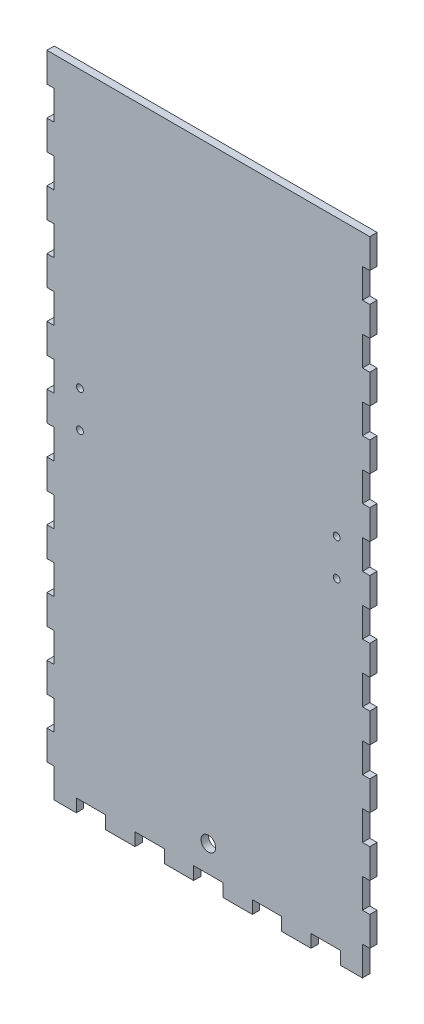
SolidWorks part; units mm, degrees
ref_plane "Front Plane" through (0, 0, 0) normal (0, 0, 1) x (1, 0, 0)
ref_plane "Top Plane" through (0, 0, 0) normal (0, 1, 0) x (1, 0, 0)
ref_plane "Right Plane" through (0, 0, 0) normal (1, 0, 0) x (0, 0, -1)
sketch "Sketch1" plane through (0, 0, 0) normal (0, 0, 1) x (1, 0, 0)
  line L0 (-66.675, 261.112) -> (-66.675, 248.412)
  line L1 (-66.675, 273.812) -> (66.675, 273.812)
  line L2 (-66.675, 273.812) -> (-66.675, 0)
  line L3 (-66.675, 0) -> (66.675, 0)
  line L4 (66.675, 273.812) -> (66.675, 0)
  line L5 (-66.675, 273.812) -> (-69.85, 273.812)
  line L6 (-66.675, 273.812) -> (-66.675, 261.112)
  line L7 (-66.675, 261.112) -> (-69.85, 261.112)
  line L8 (-69.85, 273.812) -> (-69.85, 261.112)
  line L13 (66.675, 273.812) -> (69.85, 273.812)
  line L14 (66.675, 273.812) -> (66.675, 261.112)
  line L15 (66.675, 261.112) -> (69.85, 261.112)
  line L16 (69.85, 273.812) -> (69.85, 261.112)
  line L17 (-66.675, 261.112) -> (-69.85, 261.112)
  line L18 (-69.85, 261.112) -> (-69.85, 248.412)
  line L19 (-66.675, 248.412) -> (-69.85, 248.412)
  line L20 (66.675, 261.112) -> (66.675, 248.412)
  line L21 (66.675, 261.112) -> (69.85, 261.112)
  line L22 (69.85, 261.112) -> (69.85, 248.412)
  line L23 (66.675, 248.412) -> (69.85, 248.412)
  line L24 (-66.675, 248.412) -> (-66.675, 235.712)
  line L25 (-66.675, 248.412) -> (-69.85, 248.412)
  line L26 (-69.85, 248.412) -> (-69.85, 235.712)
  line L27 (-66.675, 235.712) -> (-69.85, 235.712)
  line L28 (66.675, 248.412) -> (66.675, 235.712)
  line L29 (66.675, 248.412) -> (69.85, 248.412)
  line L30 (69.85, 248.412) -> (69.85, 235.712)
  line L31 (66.675, 235.712) -> (69.85, 235.712)
  line L32 (-66.675, 235.712) -> (-66.675, 223.012)
  line L33 (-66.675, 235.712) -> (-69.85, 235.712)
  line L34 (-69.85, 235.712) -> (-69.85, 223.012)
  line L35 (-66.675, 223.012) -> (-69.85, 223.012)
  line L36 (66.675, 235.712) -> (66.675, 223.012)
  line L37 (66.675, 235.712) -> (69.85, 235.712)
  line L38 (69.85, 235.712) -> (69.85, 223.012)
  line L39 (66.675, 223.012) -> (69.85, 223.012)
  line L40 (-66.675, 223.012) -> (-66.675, 210.312)
  line L41 (-66.675, 223.012) -> (-69.85, 223.012)
  line L42 (-69.85, 223.012) -> (-69.85, 210.312)
  line L43 (-66.675, 210.312) -> (-69.85, 210.312)
  line L44 (66.675, 223.012) -> (66.675, 210.312)
  line L45 (66.675, 223.012) -> (69.85, 223.012)
  line L46 (69.85, 223.012) -> (69.85, 210.312)
  line L47 (66.675, 210.312) -> (69.85, 210.312)
  line L48 (-66.675, 210.312) -> (-66.675, 197.612)
  line L49 (-66.675, 210.312) -> (-69.85, 210.312)
  line L50 (-69.85, 210.312) -> (-69.85, 197.612)
  line L51 (-66.675, 197.612) -> (-69.85, 197.612)
  line L52 (66.675, 210.312) -> (66.675, 197.612)
  line L53 (66.675, 210.312) -> (69.85, 210.312)
  line L54 (69.85, 210.312) -> (69.85, 197.612)
  line L55 (66.675, 197.612) -> (69.85, 197.612)
  line L56 (-66.675, 197.612) -> (-66.675, 184.912)
  line L57 (-66.675, 197.612) -> (-69.85, 197.612)
  line L58 (-69.85, 197.612) -> (-69.85, 184.912)
  line L59 (-66.675, 184.912) -> (-69.85, 184.912)
  line L60 (66.675, 197.612) -> (66.675, 184.912)
  line L61 (66.675, 197.612) -> (69.85, 197.612)
  line L62 (69.85, 197.612) -> (69.85, 184.912)
  line L63 (66.675, 184.912) -> (69.85, 184.912)
  line L64 (-66.675, 184.912) -> (-66.675, 172.212)
  line L65 (-66.675, 184.912) -> (-69.85, 184.912)
  line L66 (-69.85, 184.912) -> (-69.85, 172.212)
  line L67 (-66.675, 172.212) -> (-69.85, 172.212)
  line L68 (66.675, 184.912) -> (66.675, 172.212)
  line L69 (66.675, 184.912) -> (69.85, 184.912)
  line L70 (69.85, 184.912) -> (69.85, 172.212)
  line L71 (66.675, 172.212) -> (69.85, 172.212)
  line L72 (-66.675, 172.212) -> (-66.675, 159.512)
  line L73 (-66.675, 172.212) -> (-69.85, 172.212)
  line L74 (-69.85, 172.212) -> (-69.85, 159.512)
  line L75 (-66.675, 159.512) -> (-69.85, 159.512)
  line L76 (66.675, 172.212) -> (66.675, 159.512)
  line L77 (66.675, 172.212) -> (69.85, 172.212)
  line L78 (69.85, 172.212) -> (69.85, 159.512)
  line L79 (66.675, 159.512) -> (69.85, 159.512)
  line L80 (-66.675, 159.512) -> (-66.675, 146.812)
  line L81 (-66.675, 159.512) -> (-69.85, 159.512)
  line L82 (-69.85, 159.512) -> (-69.85, 146.812)
  line L83 (-66.675, 146.812) -> (-69.85, 146.812)
  line L84 (66.675, 159.512) -> (66.675, 146.812)
  line L85 (66.675, 159.512) -> (69.85, 159.512)
  line L86 (69.85, 159.512) -> (69.85, 146.812)
  line L87 (66.675, 146.812) -> (69.85, 146.812)
  line L88 (-66.675, 146.812) -> (-66.675, 134.112)
  line L89 (-66.675, 146.812) -> (-69.85, 146.812)
  line L90 (-69.85, 146.812) -> (-69.85, 134.112)
  line L91 (-66.675, 134.112) -> (-69.85, 134.112)
  line L92 (66.675, 146.812) -> (66.675, 134.112)
  line L93 (66.675, 146.812) -> (69.85, 146.812)
  line L94 (69.85, 146.812) -> (69.85, 134.112)
  line L95 (66.675, 134.112) -> (69.85, 134.112)
  line L96 (-66.675, 134.112) -> (-66.675, 121.412)
  line L97 (-66.675, 134.112) -> (-69.85, 134.112)
  line L98 (-69.85, 134.112) -> (-69.85, 121.412)
  line L99 (-66.675, 121.412) -> (-69.85, 121.412)
  line L100 (66.675, 134.112) -> (66.675, 121.412)
  line L101 (66.675, 134.112) -> (69.85, 134.112)
  line L102 (69.85, 134.112) -> (69.85, 121.412)
  line L103 (66.675, 121.412) -> (69.85, 121.412)
  line L104 (-66.675, 121.412) -> (-66.675, 108.712)
  line L105 (-66.675, 121.412) -> (-69.85, 121.412)
  line L106 (-69.85, 121.412) -> (-69.85, 108.712)
  line L107 (-66.675, 108.712) -> (-69.85, 108.712)
  line L108 (66.675, 121.412) -> (66.675, 108.712)
  line L109 (66.675, 121.412) -> (69.85, 121.412)
  line L110 (69.85, 121.412) -> (69.85, 108.712)
  line L111 (66.675, 108.712) -> (69.85, 108.712)
  line L112 (-66.675, 108.712) -> (-66.675, 96.012)
  line L113 (-66.675, 108.712) -> (-69.85, 108.712)
  line L114 (-69.85, 108.712) -> (-69.85, 96.012)
  line L115 (-66.675, 96.012) -> (-69.85, 96.012)
  line L116 (66.675, 108.712) -> (66.675, 96.012)
  line L117 (66.675, 108.712) -> (69.85, 108.712)
  line L118 (69.85, 108.712) -> (69.85, 96.012)
  line L119 (66.675, 96.012) -> (69.85, 96.012)
  line L120 (-66.675, 96.012) -> (-66.675, 83.312)
  line L121 (-66.675, 96.012) -> (-69.85, 96.012)
  line L122 (-69.85, 96.012) -> (-69.85, 83.312)
  line L123 (-66.675, 83.312) -> (-69.85, 83.312)
  line L124 (66.675, 96.012) -> (66.675, 83.312)
  line L125 (66.675, 96.012) -> (69.85, 96.012)
  line L126 (69.85, 96.012) -> (69.85, 83.312)
  line L127 (66.675, 83.312) -> (69.85, 83.312)
  line L128 (-66.675, 83.312) -> (-66.675, 70.612)
  line L129 (-66.675, 83.312) -> (-69.85, 83.312)
  line L130 (-69.85, 83.312) -> (-69.85, 70.612)
  line L131 (-66.675, 70.612) -> (-69.85, 70.612)
  line L132 (66.675, 83.312) -> (66.675, 70.612)
  line L133 (66.675, 83.312) -> (69.85, 83.312)
  line L134 (69.85, 83.312) -> (69.85, 70.612)
  line L135 (66.675, 70.612) -> (69.85, 70.612)
  line L136 (-66.675, 70.612) -> (-66.675, 57.912)
  line L137 (-66.675, 70.612) -> (-69.85, 70.612)
  line L138 (-69.85, 70.612) -> (-69.85, 57.912)
  line L139 (-66.675, 57.912) -> (-69.85, 57.912)
  line L140 (66.675, 70.612) -> (66.675, 57.912)
  line L141 (66.675, 70.612) -> (69.85, 70.612)
  line L142 (69.85, 70.612) -> (69.85, 57.912)
  line L143 (66.675, 57.912) -> (69.85, 57.912)
  line L144 (-66.675, 57.912) -> (-66.675, 45.212)
  line L145 (-66.675, 57.912) -> (-69.85, 57.912)
  line L146 (-69.85, 57.912) -> (-69.85, 45.212)
  line L147 (-66.675, 45.212) -> (-69.85, 45.212)
  line L148 (66.675, 57.912) -> (66.675, 45.212)
  line L149 (66.675, 57.912) -> (69.85, 57.912)
  line L150 (69.85, 57.912) -> (69.85, 45.212)
  line L151 (66.675, 45.212) -> (69.85, 45.212)
  line L152 (-66.675, 45.212) -> (-66.675, 32.512)
  line L153 (-66.675, 45.212) -> (-69.85, 45.212)
  line L154 (-69.85, 45.212) -> (-69.85, 32.512)
  line L155 (-66.675, 32.512) -> (-69.85, 32.512)
  line L156 (66.675, 45.212) -> (66.675, 32.512)
  line L157 (66.675, 45.212) -> (69.85, 45.212)
  line L158 (69.85, 45.212) -> (69.85, 32.512)
  line L159 (66.675, 32.512) -> (69.85, 32.512)
  line L160 (-66.675, 32.512) -> (-66.675, 19.812)
  line L161 (-66.675, 32.512) -> (-69.85, 32.512)
  line L162 (-69.85, 32.512) -> (-69.85, 19.812)
  line L163 (-66.675, 19.812) -> (-69.85, 19.812)
  line L164 (66.675, 32.512) -> (66.675, 19.812)
  line L165 (66.675, 32.512) -> (69.85, 32.512)
  line L166 (69.85, 32.512) -> (69.85, 19.812)
  line L167 (66.675, 19.812) -> (69.85, 19.812)
  line L168 (-66.675, 19.812) -> (-66.675, 7.112)
  line L169 (-66.675, 19.812) -> (-69.85, 19.812)
  line L170 (-69.85, 19.812) -> (-69.85, 7.112)
  line L171 (-66.675, 7.112) -> (-69.85, 7.112)
  line L172 (66.675, 19.812) -> (66.675, 7.112)
  line L173 (66.675, 19.812) -> (69.85, 19.812)
  line L174 (69.85, 19.812) -> (69.85, 7.112)
  line L175 (66.675, 7.112) -> (69.85, 7.112)
  line L176 (-66.675, 7.112) -> (-66.675, -5.588)
  line L177 (-66.675, 7.112) -> (-69.85, 7.112)
  line L178 (-69.85, 7.112) -> (-69.85, -5.588)
  line L179 (-66.675, -5.588) -> (-69.85, -5.588)
  line L180 (66.675, 7.112) -> (66.675, -5.588)
  line L181 (66.675, 7.112) -> (69.85, 7.112)
  line L182 (69.85, 7.112) -> (69.85, -5.588)
  line L183 (66.675, -5.588) -> (69.85, -5.588)
  line L184 (-57.15, 0) -> (-57.15, -5.588)
  line L185 (-69.85, 0) -> (-57.15, 0)
  line L186 (-69.85, 0) -> (-69.85, -5.588)
  line L187 (-69.85, -5.588) -> (-57.15, -5.588)
  line L188 (-57.15, 0) -> (-57.15, -5.588)
  line L189 (-57.15, 0) -> (-44.45, 0)
  line L190 (-44.45, 0) -> (-44.45, -5.588)
  line L191 (-57.15, -5.588) -> (-44.45, -5.588)
  line L192 (-44.45, 0) -> (-44.45, -5.588)
  line L193 (-44.45, 0) -> (-31.75, 0)
  line L194 (-31.75, 0) -> (-31.75, -5.588)
  line L195 (-44.45, -5.588) -> (-31.75, -5.588)
  line L196 (-31.75, 0) -> (-31.75, -5.588)
  line L197 (-31.75, 0) -> (-19.05, 0)
  line L198 (-19.05, 0) -> (-19.05, -5.588)
  line L199 (-31.75, -5.588) -> (-19.05, -5.588)
  line L200 (-19.05, 0) -> (-19.05, -5.588)
  line L201 (-19.05, 0) -> (-6.35, 0)
  line L202 (-6.35, 0) -> (-6.35, -5.588)
  line L203 (-19.05, -5.588) -> (-6.35, -5.588)
  line L204 (-6.35, 0) -> (-6.35, -5.588)
  line L205 (-6.35, 0) -> (6.35, 0)
  line L206 (6.35, 0) -> (6.35, -5.588)
  line L207 (-6.35, -5.588) -> (6.35, -5.588)
  line L208 (6.35, 0) -> (6.35, -5.588)
  line L209 (6.35, 0) -> (19.05, 0)
  line L210 (19.05, 0) -> (19.05, -5.588)
  line L211 (6.35, -5.588) -> (19.05, -5.588)
  line L212 (19.05, 0) -> (19.05, -5.588)
  line L213 (19.05, 0) -> (31.75, 0)
  line L214 (31.75, 0) -> (31.75, -5.588)
  line L215 (19.05, -5.588) -> (31.75, -5.588)
  line L216 (31.75, 0) -> (31.75, -5.588)
  line L217 (31.75, 0) -> (44.45, 0)
  line L218 (44.45, 0) -> (44.45, -5.588)
  line L219 (31.75, -5.588) -> (44.45, -5.588)
  line L220 (44.45, 0) -> (44.45, -5.588)
  line L221 (44.45, 0) -> (57.15, 0)
  line L222 (57.15, 0) -> (57.15, -5.588)
  line L223 (44.45, -5.588) -> (57.15, -5.588)
  line L224 (57.15, 0) -> (57.15, -5.588)
  line L225 (57.15, 0) -> (69.85, 0)
  line L226 (69.85, 0) -> (69.85, -5.588)
  line L227 (57.15, -5.588) -> (69.85, -5.588)
  point P4 (0, 0)
  dimension "D1" = 133.35
  dimension "D2" = 273.812
  dimension "D3" = 139.7
  dimension "D6" = 279.4
  dimension "D7" = 12.7
  dimension "D8" = 12.7
  dimension "D4" = 22
  dimension "D5" = 11
extrude "Boss-Extrude1" add sketch "Sketch1" along normal blind 3.175 contours L4 L1 L2 L0 L3 | L171 L2 L163 L170 | L155 L2 L147 L154 | L139 L2 L131 L138 | L123 L2 L115 L122 | L176 L187 L184 L3 | L190 L195 L194 L3 | L198 L203 L202 L3 | L206 L211 L210 L3 | L214 L219 L218 L3 | L222 L227 L180 L3 | L4 L175 L174 L167 | L4 L159 L158 L151 | L4 L143 L142 L135 | L4 L127 L126 L119 | L4 L111 L110 L103 | L107 L2 L99 L106 | L91 L2 L83 L90 | L75 L2 L67 L74 | L59 L2 L51 L58 | L43 L2 L35 L42 | L27 L2 L19 L26 | L5 L8 L7 L2 | L4 L95 L94 L87 | L4 L79 L78 L71 | L4 L63 L62 L55 | L4 L47 L46 L39 | L4 L31 L30 L23 | L16 L13 L4 L15 region at (0, 136.906, 0) region at (-68.2625, 267.462, 0) region at (-68.2625, 242.062, 0) region at (68.2625, 267.462, 0) region at (-68.2625, 216.662, 0) region at (68.2625, 242.062, 0) region at (-68.2625, 191.262, 0) region at (68.2625, 216.662, 0) region at (-68.2625, 165.862, 0) region at (68.2625, 191.262, 0) region at (-68.2625, 140.462, 0) region at (68.2625, 165.862, 0) region at (-68.2625, 115.062, 0) region at (68.2625, 140.462, 0) region at (-68.2625, 89.662, 0) region at (68.2625, 115.062, 0) region at (-68.2625, 64.262, 0) region at (68.2625, 89.662, 0) region at (-68.2625, 38.862, 0) region at (68.2625, 64.262, 0) region at (-68.2625, 13.462, 0) region at (68.2625, 38.862, 0) region at (-61.9125, -2.794, 0) region at (68.2625, 13.462, 0) region at (-38.1, -2.794, 0) region at (61.9125, -2.794, 0) region at (-12.7, -2.794, 0) region at (38.1, -2.794, 0) region at (12.7, -2.794, 0)
sketch "Sketch2" plane through (0, 0, 3.175) normal (0, 0, 1) x (1, 0, 0)
  circle A0 centre (0, 11.43) radius 3.175
  dimension "D2" = 6.35
  dimension "D1" = 11.43
extrude "Cut-Extrude1" cut sketch "Sketch2" against normal through all
sketch "Sketch3" plane through (0, 0, 3.175) normal (0, 0, 1) x (1, 0, 0)
  line L0 (-55.5625, 154.305) -> (-55.5625, 138.557) construction
  line L1 (55.5625, 154.305) -> (55.5625, 138.557) construction
  line L2 (-55.5625, 146.431) -> (55.5625, 146.431) construction
  line L3 (-57.15, 0) -> (-44.45, 0) construction
  line L5 (-69.85, 146.812) -> (-69.85, 134.112) construction
  circle A0 centre (-55.5625, 154.305) radius 1.5
  circle A1 centre (-55.5625, 138.557) radius 1.5
  circle A2 centre (55.5625, 154.305) radius 1.5
  circle A3 centre (55.5625, 138.557) radius 1.5
  point P10 (0, 146.431)
  dimension "D2" = 3
  dimension "D3" = 138.557
  dimension "D4" = 14.2875
  dimension "D1" = 15.748
extrude "Cut-Extrude2" cut sketch "Sketch3" against normal through all
sketch "Sketch4" plane through (0, 0, 3.175) normal (0, 0, 1) x (1, 0, 0)
  line L0 (-69.85, 273.812) -> (69.85, 273.812) construction
  line L1 (-66.675, 273.812) -> (66.675, 273.812)
  line L2 (-66.675, 273.812) -> (-66.675, 299.212)
  line L3 (-66.675, 299.212) -> (66.675, 299.212)
  line L4 (66.675, 273.812) -> (66.675, 299.212)
  dimension "D1" = 25.4
extrude "Boss-Extrude2" [suppressed] add sketch "Sketch4" against normal up to surface (3.175 mm away) up to face at (-54.0625, 138.557, 0)
equation "\"bottomThickness\"= .220in"
equation "\"wallThickness\"= .125in"
equation "\"D3@Sketch1\"=2*\"wallThickness\"+5.25"
equation "\"D6@Sketch1\"=\"bottomThickness\"+10.78"
equation "\"D7@Sketch1\"=\"D6@Sketch1\"/\"D4@Sketch1\""
equation "\"D8@Sketch1\"=\"D3@Sketch1\"/\"D5@Sketch1\""
equation "\"D1@Boss-Extrude1\"=\"wallThickness\""
